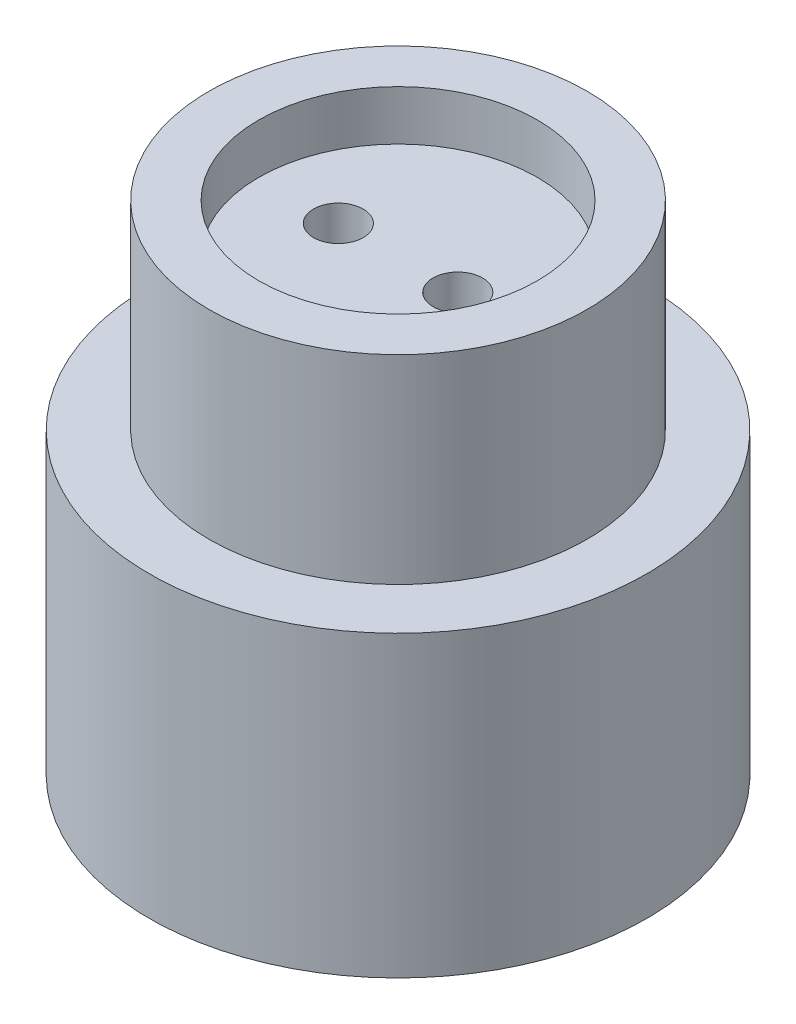
SolidWorks part; units mm, degrees
ref_plane "Front Plane" through (0, 0, 0) normal (0, 0, 1) x (1, 0, 0)
ref_plane "Top Plane" through (0, 0, 0) normal (0, 1, 0) x (1, 0, 0)
ref_plane "Right Plane" through (0, 0, 0) normal (1, 0, 0) x (0, 0, -1)
sketch "Sketch2" plane through (0, 0, 0) normal (1, 0, 0) x (0, 0, -1)
  line L0 (0, 0) -> (2.5, 0)
  line L1 (2.5, 0) -> (2.5, 3)
  line L2 (2.5, 3) -> (1.9, 3)
  line L3 (1.9, 3) -> (1.9, 5)
  line L6 (0, 0) -> (0, 6.9206) construction
  line L7 (0, 0.5) -> (2, 0.5)
  line L8 (2, 0.5) -> (2, 2.5)
  line L9 (2, 2.5) -> (1.4, 2.5)
  line L10 (1.4, 2.5) -> (1.4, 5)
  line L11 (1.4, 5) -> (1.9, 5)
  line L12 (0, 0.5) -> (0, 0)
  dimension "D1" = 2
  dimension "D2" = 3
  dimension "D3" = 2.5
  dimension "D5" = 0.6
  dimension "D4" = 0.5
revolve "Revolve1" add sketch "Sketch2" angle 360 about L6
ref_plane "Plane1" through (0, 4.5, 0) normal (0, 1, 0) x (1, 0, 0)
sketch "Sketch3" plane through (0, 4.5, 0) normal (0, 1, 0) x (1, 0, 0)
  circle A0 centre (0, 0) radius 1.4
  circle A1 centre (0, 0) radius 1.4 construction
extrude "Boss-Extrude1" add sketch "Sketch3" against normal blind 0.3
sketch "Sketch4" plane through (0, 4.5, 0) normal (0, 1, 0) x (1, 0, 0)
  circle A0 centre (0.6, 0) radius 0.2493
  circle A1 centre (0.6, 0) radius 0.3493
  dimension "D2" = 0.4987
  dimension "D1" = 0.6
  dimension "D3" = 0.1
sketch "Sketch5" plane through (0, 0, 0) normal (0, 0, 1) x (1, 0, 0)
  line L0 (0.6, 4.5) -> (0.6, 2)
  line L1 (0.8493, 4.5) -> (0.3507, 4.5) construction
  line L2 (0.6, 2) -> (1.3, 2)
  line L3 (1.3, 2) -> (1.3, 0.5)
  line L4 (2, 0.5) -> (-2, 0.5) construction
  line L5 (-2.5, 0) -> (2.5, 0) construction
  point P12 (0.8922, 2)
  dimension "D1" = 2
  dimension "D2" = 0.7
sweep "Sweep2" add profiles "Sketch4" path "Sketch5"
sketch "Sketch8" plane through (0, 0.5, 0) normal (0, 1, 0) x (1, 0, 0)
  circle A0 centre (1.3, 0) radius 0.2493
extrude "Cut-Extrude6" cut sketch "Sketch8" against normal blind 0.7
extrude "Cut-Extrude7" cut sketch "Sketch4<5>" against normal blind 0.3 contours A0
sketch "Sketch4<5>" plane through (0, 4.5, 0) normal (0, 1, 0) x (1, 0, 0) same geometry as "Sketch4"
sketch "Sketch10" plane through (0, 0, 0) normal (0, 0, 1) x (1, 0, 0)
  line L0 (0, 5) -> (0, 0) construction
  line L1 (1.4, 5) -> (-1.4, 5) construction
mirror "Mirror1" about plane through (0, 0, 0) normal (1, 0, 0) of "Cut-Extrude6", "Cut-Extrude7", "Sweep2"
